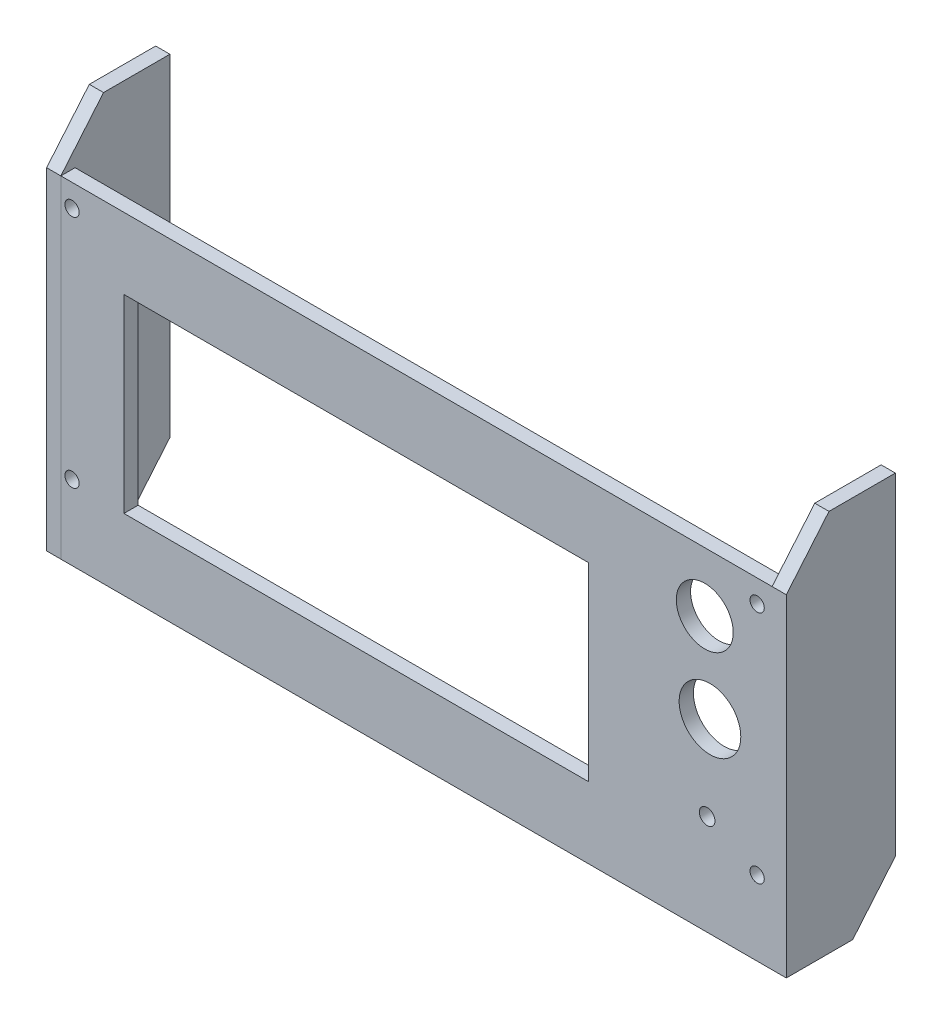
SolidWorks part; units mm, degrees
ref_plane "Alzado" through (0, 0, 0) normal (0, 0, 1) x (1, 0, 0)
ref_plane "Planta" through (0, 0, 0) normal (0, 1, 0) x (1, 0, 0)
ref_plane "Vista lateral" through (0, 0, 0) normal (1, 0, 0) x (0, 0, -1)
sketch "Croquis1" plane through (0, 0, 0) normal (0, 0, 1) x (1, 0, 0)
  line L0 (0, 0) -> (0, 70)
  line L1 (0, 70) -> (150, 70)
  line L2 (150, 70) -> (150, 0)
  line L3 (150, 0) -> (0, 0)
  circle A0 centre (135.8, 57.5) radius 6
  dimension "D1" = 70
  dimension "D2" = 150
extrude "Saliente-Extruir1" add sketch "Croquis1" along normal blind 3
sketch "Croquis2" plane through (0, 0, 3) normal (0, 0, 1) x (1, 0, 0)
  line L0 (13.3, 15) -> (13.3, 55)
  line L1 (13.3, 55) -> (111.3, 55)
  line L2 (111.3, 55) -> (111.3, 15)
  line L3 (111.3, 15) -> (13.3, 15)
  dimension "D1" = 98
  dimension "D2" = 40
  dimension "D3" = 15
  dimension "D4" = 13.3
extrude "Cortar-Extruir1" cut sketch "Croquis2" against normal blind 3
sketch "Croquis3" plane through (0, 0, 3) normal (0, 0, 1) x (1, 0, 0)
  circle A0 centre (136.9, 39.25) radius 6.5
  dimension "D1" = 13
extrude "Cortar-Extruir2" cut sketch "Croquis3" against normal through all
sketch "Croquis4" plane through (0, 0, 3) normal (0, 0, 1) x (1, 0, 0)
  circle A1 centre (136.3, 21.15) radius 1.65 construction
  circle A2 centre (136.3, 21.15) radius 1.65
extrude "Cortar-Extruir3" cut sketch "Croquis4" against normal blind 3
sketch "Croquis5" plane through (0, 0, 3) normal (0, 0, 1) x (1, 0, 0)
  circle A0 centre (146.85, 65.25) radius 1.5 construction
  circle A1 centre (146.85, 15.75) radius 1.5 construction
  circle A2 centre (2.35, 15.75) radius 1.5 construction
  circle A3 centre (2.35, 65.25) radius 1.5 construction
  circle A4 centre (146.85, 65.25) radius 1.5
  circle A5 centre (146.85, 15.75) radius 1.5
  circle A6 centre (2.35, 15.75) radius 1.5
  circle A7 centre (2.35, 65.25) radius 1.5
extrude "Cortar-Extruir4" cut sketch "Croquis5" against normal blind 3
sketch "Croquis7" plane through (150, 0, 0) normal (1, 0, 0) x (0, 0, -1)
  line L0 (-3, 70) -> (6, 80.7258)
  line L1 (6, 80.7258) -> (20, 80.7258)
  line L2 (20, 80.7258) -> (20, 10.7258)
  line L3 (20, 10.7258) -> (11, 0)
  line L4 (11, 0) -> (-3, 0)
  line L5 (-3, 70) -> (3.6334, 70) construction
  line L6 (11, 0) -> (26.1167, 0) construction
  line L7 (-3, 70) -> (-3, 0)
  dimension "D1" = 50
  dimension "D2" = 14
  dimension "D3" = 9
  dimension "D4" = 9
extrude "Saliente-Extruir4" add sketch "Croquis7" along normal blind 3
sketch "Croquis9" plane through (0, 0, 0) normal (-1, 0, 0) x (0, 0, 1)
  line L0 (3, 70) -> (3, 0) construction
  line L1 (0, 0) -> (-11, 0) construction
  line L2 (-11, 0) -> (-20, 10.7258) construction
  line L3 (-20, 10.7258) -> (-20, 80.7258) construction
  line L4 (-6, 80.7258) -> (3, 70) construction
  line L5 (3, 70) -> (3, 0)
  line L6 (0, 0) -> (-11, 0)
  line L7 (-11, 0) -> (-20, 10.7258)
  line L8 (-20, 10.7258) -> (-20, 80.7258)
  line L9 (-6, 80.7258) -> (3, 70)
  line L10 (-20, 80.7258) -> (-6, 80.7258) construction
  line L11 (-20, 80.7258) -> (-6, 80.7258)
  line M1 (0, 70) -> (0, 0)
  line M2 (0, 0) -> (3, 0)
  line M3 (3, 0) -> (3, 70)
  line M4 (3, 70) -> (0, 70)
extrude "Saliente-Extruir5" add sketch "Croquis9" along normal blind 3 separate body contours L11 L8 L7 L6 L9 M1 M4 | M4 M1 M2 M3 region at (0, 41.0894, -9.8547) region at (0, 35, 1.5)
